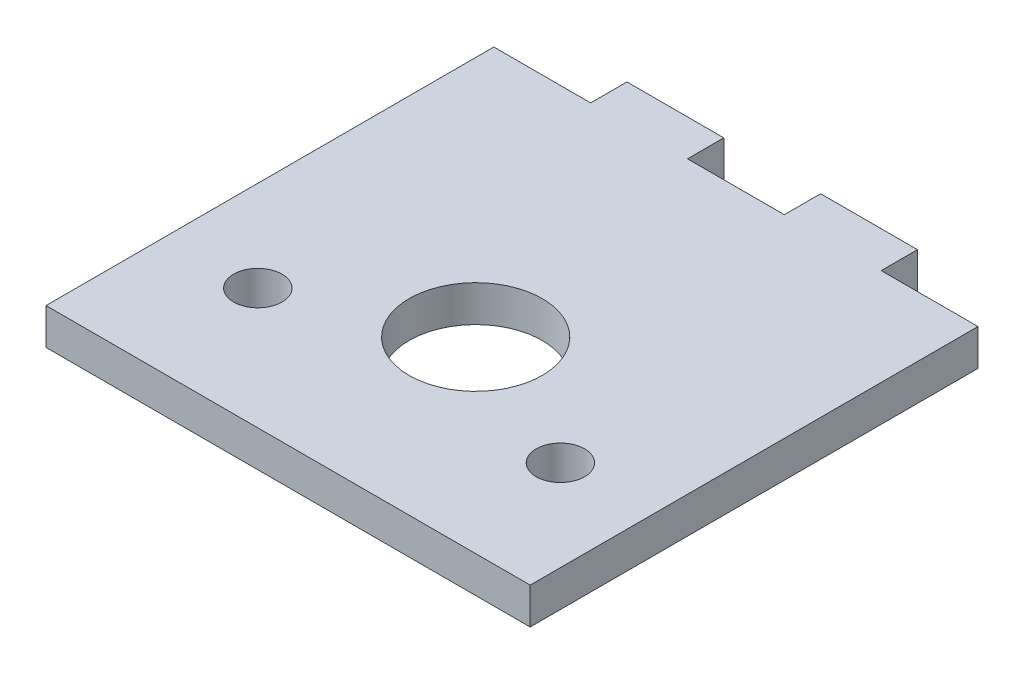
SolidWorks part; units mm, degrees
material "Acrylic (Medium-high impact)"
ref_plane "Front Plane" through (0, 0, 0) normal (0, 0, 1) x (1, 0, 0)
ref_plane "Top Plane" through (0, 0, 0) normal (0, 1, 0) x (1, 0, 0)
ref_plane "Right Plane" through (0, 0, 0) normal (1, 0, 0) x (0, 0, -1)
sketch "Sketch1" plane through (0, 0, 0) normal (0, 1, 0) x (1, 0, 0)
  line L0 (-1000, 0) -> (49000, 0) construction
  line L5 (0, -1000) -> (0, 49000) construction
  line L6 (-40, 43) -> (-24, 43)
  line L7 (-40, -31) -> (40, -31)
  line L8 (-40, -31) -> (-40, 43)
  line L9 (-24, 49) -> (-8, 49)
  line L10 (40, -31) -> (40, 43)
  line L11 (-24, 49) -> (-24, 43)
  line L12 (-8, 49) -> (-8, 43)
  line L13 (8, 49) -> (8, 43)
  line L14 (24, 49) -> (24, 43)
  line L16 (24, 43) -> (40, 43)
  line L17 (8, 49) -> (24, 49)
  line L18 (-8, 43) -> (8, 43)
  circle A10 centre (0, 0) radius 4
  circle A15 centre (25, -11) radius 4
  circle A16 centre (-25, -11) radius 4
  point P6 (0, 43)
  dimension "D3" = 8
  dimension "D4" = 20
  dimension "D12" = 8
  dimension "D2" = 80
  dimension "D5" = 31
  dimension "D7" = 6
  dimension "D9" = 4
  dimension "D8" = 16
  dimension "D10" = 16
  dimension "D11" = 80
  dimension "D13" = 25
extrude "Boss-Extrude1" add sketch "Sketch1" along normal blind 6
sketch "Sketch2" plane through (0, 6, 0) normal (0, 1, 0) x (1, 0, 0)
  circle A0 centre (0, 0) radius 11
  dimension "D1" = 22
extrude "Cut-Extrude1" cut sketch "Sketch2" against normal up to next
